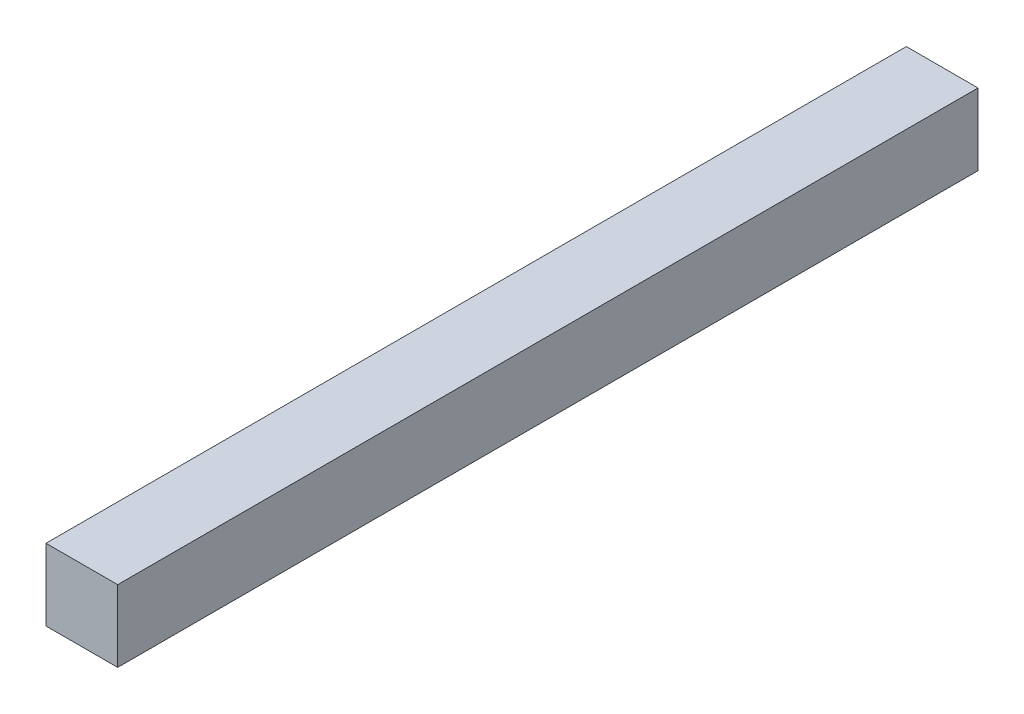
SolidWorks part; units mm, degrees
material "Pine"
ref_plane "Front Plane" through (0, 0, 0) normal (0, 0, 1) x (1, 0, 0)
ref_plane "Top Plane" through (0, 0, 0) normal (0, 1, 0) x (1, 0, 0)
ref_plane "Right Plane" through (0, 0, 0) normal (1, 0, 0) x (0, 0, -1)
sketch "Sketch1" plane through (0, 0, 0) normal (0, 0, 1) x (1, 0, 0)
  line L1 (-8.7312, 31.8492) -> (29.3688, 31.8492)
  line L2 (-8.7312, 31.8492) -> (-8.7312, -6.2508)
  line L3 (-8.7312, -6.2508) -> (29.3688, -6.2508)
  line L4 (29.3688, 31.8492) -> (29.3688, -6.2508)
  dimension "D1" = 38.1
  dimension "D2" = 38.1
extrude "Boss-Extrude1" add sketch "Sketch1" along normal blind 457.2
